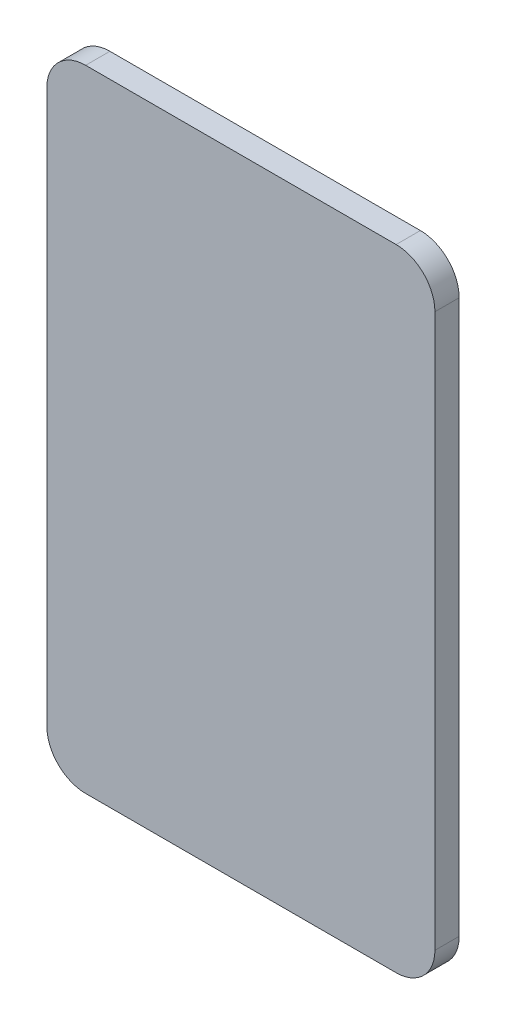
SolidWorks part; units mm, degrees
ref_plane "Front Plane" through (0, 0, 0) normal (0, 0, 1) x (1, 0, 0)
ref_plane "Top Plane" through (0, 0, 0) normal (0, 1, 0) x (1, 0, 0)
ref_plane "Right Plane" through (0, 0, 0) normal (1, 0, 0) x (0, 0, -1)
sketch "Sketch1" plane through (0, 0, 0) normal (0, 0, 1) x (1, 0, 0)
  line L1 (-32, 65) -> (32, 65)
  line L2 (-40, 57) -> (-40, -57)
  line L3 (-32, -65) -> (32, -65)
  line L4 (40, 57) -> (40, -57)
  line L5 (-40, 65) -> (40, -65) construction
  line L6 (-40, -65) -> (40, 65) construction
  arc A0 (40, 57) -> (32, 65) centre (32, 57) ccw
  arc A1 (40, -57) -> (32, -65) centre (32, -57) cw
  arc A2 (-32, -65) -> (-40, -57) centre (-32, -57) cw
  arc A3 (-32, 65) -> (-40, 57) centre (-32, 57) ccw
  point P0 (0, 0)
  dimension "D1" = 8
  dimension "D2" = 64
extrude "Boss-Extrude1" add sketch "Sketch1" along normal blind 5
